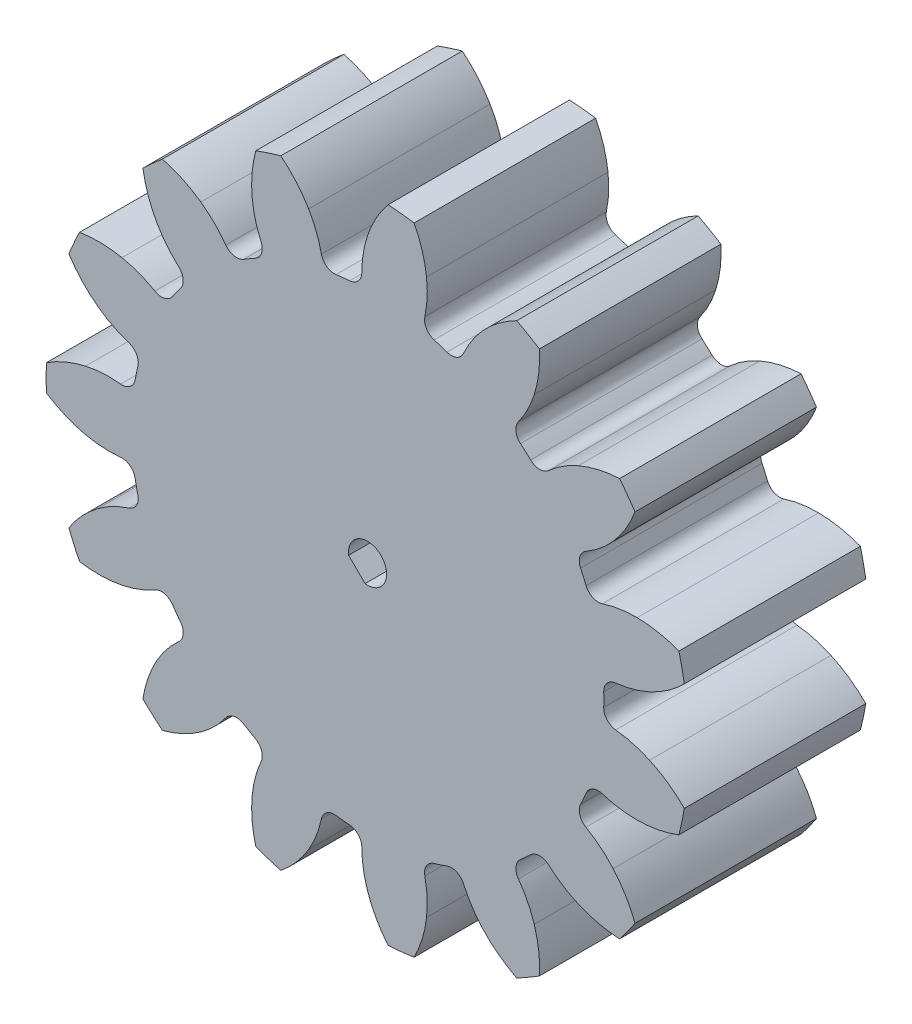
SolidWorks part; units mm, degrees
ref_plane "Front Plane" through (0, 0, 0) normal (0, 0, 1) x (1, 0, 0)
ref_plane "Top Plane" through (0, 0, 0) normal (0, 1, 0) x (1, 0, 0)
ref_plane "Right Plane" through (0, 0, 0) normal (1, 0, 0) x (0, 0, -1)
sketch "Sketch1" plane through (0, 0, 0) normal (0, 0, 1) x (1, 0, 0)
  line L0 (0, 0) -> (23.8125, 0) construction
  line L1 (23.8125, 0) -> (26.9875, 0) construction
  circle A0 centre (0, 0) radius 26.9875
  circle A1 centre (0, 0) radius 23.8125 construction
  dimension "D2" = 47.625
  dimension "D1" = 3.175
extrude "GEAR_BASE" add sketch "Sketch1" along normal mid plane 15.24
sketch "Sketch2" plane through (0, 0, 7.62) normal (0, 0, 1) x (1, 0, 0)
  line L0 (0, 0) -> (19.8438, 0) construction
  line L1 (19.8438, 0) -> (23.8125, 0) construction
  line L2 (0, 0) -> (-26.9875, 0) construction
  line L3 (0, 0) -> (-23.6815, -2.494) construction
  line L4 (-23.6815, -2.494) -> (-25.0117, 10.1362) construction
  line L5 (0, 0) -> (-24.6543, -10.9768) construction
  line L6 (-23.6815, -2.494) -> (-19.6587, -2.704) construction
  line L7 (-22.6485, -7.3538) -> (-19.0589, -5.5257) construction
  line L8 (0, 0) -> (-22.6485, -7.3538) construction
  line L9 (-23.6815, -2.494) -> (-26.965, -1.101) construction
  line L10 (-22.6485, -7.3538) -> (-25.0816, -9.9619) construction
  line L11 (-22.6485, -7.3538) -> (-21.6342, -9.6321) construction
  line L12 (-22.6485, -7.3538) -> (-18.7265, -19.433) construction
  line L13 (-23.6815, -2.494) -> (-23.6815, 0) construction
  circle A0 centre (0, 0) radius 23.8125 construction
  circle A1 centre (0, 0) radius 19.8438 construction
  circle A2 centre (0, 0) radius 26.9875 construction
  arc A3 (-25.0816, -9.9619) -> (-26.965, -1.101) centre (0, 0) cw
  arc A4 (-19.5205, -3.5671) -> (-20.733, -2.662) centre (-20.6137, -3.7669) ccw
  arc A5 (-20.0233, -6.001) -> (-19.2837, -4.681) centre (-20.3636, -4.9431) ccw
  arc A6 (-19.2837, -4.681) -> (-19.5205, -3.5671) centre (0, 0) cw
  arc A7 (-25.0816, -9.9619) -> (-22.6485, -7.3538) centre (-16.6881, -15.3532) cw
  arc A8 (-26.965, -1.101) -> (-23.6815, -2.494) centre (-21.4901, 7.2382) ccw
  arc A9 (-22.6485, -7.3538) -> (-20.0233, -6.001) centre (-17.2621, -14.5829) cw
  arc A10 (-23.6815, -2.494) -> (-20.733, -2.662) centre (-21.7011, 6.301) ccw
  dimension "D1" = 47.625
  dimension "D11" = 1.1112
  dimension "D12" = 9.9758
  dimension "D2" = 3.9688
  dimension "D3" = 24
  dimension "D5" = 9
  dimension "D7" = 9
  dimension "D8" = 4.9684
  dimension "D9" = 20
  dimension "D10" = 20
  dimension "D6" = 2.494
  dimension "D4" = 2.494
extrude "GEAR_CUT" cut sketch "Sketch2" against normal through all
ref_axis "GEAR_AXIS" through (0, 0, -1.397) along (0, 0, 1)
pattern_circular "GEAR_TEETH" count 15 over 360 about axis through (0, 0, -1.397) along (0, 0, 1) of "GEAR_CUT"
sketch "Sketch3" plane through (0, 0, 7.62) normal (0, 0, 1) x (1, 0, 0)
  line L0 (-1.5856, -0.2153) -> (-0.2039, -1.5872)
  line L1 (0, 0) -> (-0.8948, -0.9013) construction
  circle A0 centre (0, 0) radius 1.6002
  dimension "D1" = 3.2004
  dimension "D2" = 1.27
extrude "Cut-Extrude1" cut sketch "Sketch3" against normal through all contours L0 A0 region at (0.057, 0.0574, 7.62)
equation "\"N_teeth\"= 15"
equation "\"pitch_diameter\"= \"N_teeth\" / \"Pitch\""
equation "\"Pitch\"= 8"
equation "\"addendum\"=1.000/\"Pitch\""
equation "\"face_width\"=0.23"
equation "\"deddendum\"=1.250/\"Pitch\""
equation "\"tooth_thickness\"=1.571/\"Pitch\""
equation "\"Pressure_Angle\"=20.000000"
equation "\"base_fillet\"=0.35/\"Pitch\""
equation "\"D1@Sketch1\"=\"addendum\""
equation "\"D2@Sketch1\"=\"pitch_diameter\""
equation "\"D1@GEAR_BASE\"=\"GMaterial\""
equation "\"D1@Sketch2\"= \"pitch_diameter\""
equation "\"D2@Sketch2\"=\"deddendum\""
equation "\"D4@Sketch2\"=\"tooth_thickness\"/2"
equation "\"D6@Sketch2\"=\"tooth_thickness\"/2"
equation "\"D9@Sketch2\"=\"Pressure_Angle\""
equation "\"D10@Sketch2\"=\"Pressure_Angle\""
equation "\"D11@Sketch2\"=\"base_fillet\""
equation "\"D12@Sketch2\"=2*\"tooth_thickness\""
equation "\"D3@Sketch2\" = 360 / \"N_teeth\""
equation "\"D1@GEAR_TEETH\" = \"N_teeth\""
equation "\"MDF\"= .6"
equation "\"Foamcore\"= .1"
equation "\"GMaterial\"= \"MDF\""
